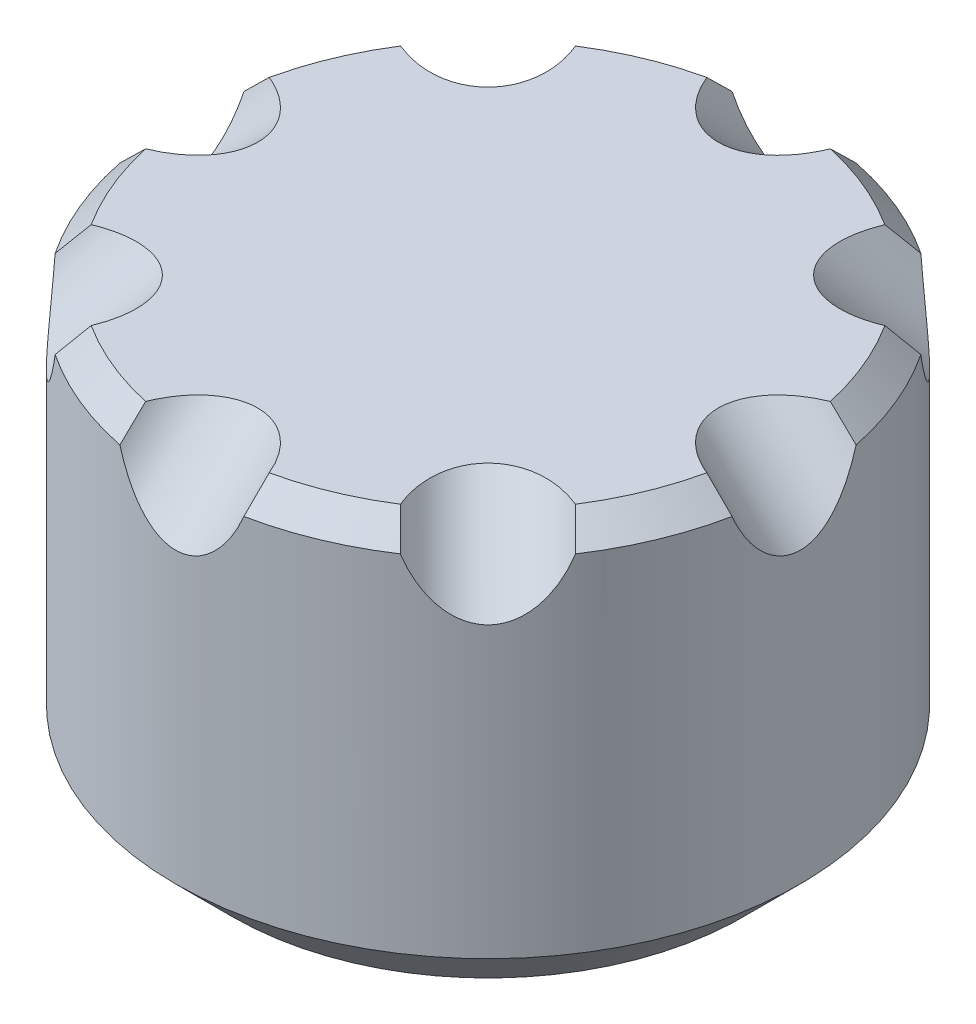
SolidWorks part; units mm, degrees
ref_plane "Front Plane" through (0, 0, 0) normal (0, 0, 1) x (1, 0, 0)
ref_plane "Top Plane" through (0, 0, 0) normal (0, 1, 0) x (1, 0, 0)
ref_plane "Right Plane" through (0, 0, 0) normal (1, 0, 0) x (0, 0, -1)
sketch "Sketch1" plane through (0, 0, 0) normal (0, 1, 0) x (1, 0, 0)
  circle A0 centre (0, 0) radius 8.75
  dimension "D1" = 17.5
extrude "Boss-Extrude1" add sketch "Sketch1" along normal blind 12
sketch "Sketch2" plane through (0, 0, 0) normal (0, -1, 0) x (1, 0, 0)
  line L0 (-2.5981, 1.5) -> (2.5981, 1.5) construction
  line L1 (-2.6439, 1.58) -> (2.6439, 1.58)
  arc A0 (-2.5981, 1.5) -> (2.5981, 1.5) centre (0, 0) ccw construction
  arc A1 (-2.6439, 1.58) -> (2.6439, 1.58) centre (0, 0) ccw
  point P5 (0, -3)
  dimension "D1" = 6
  dimension "D2" = 4.5
  dimension "D3" = 0.08
extrude "Cut-Extrude1" cut sketch "Sketch2" against normal offset from surface (11.4 mm away) 0.6 up to face at (0, 12, 8.75)
sketch "Sketch3" plane through (0, 0, 0) normal (0, -1, 0) x (1, 0, 0)
  circle A0 centre (0, 0) radius 3.08
  arc A1 (-2.6439, 1.58) -> (2.6439, 1.58) centre (0, 0) ccw construction
sketch "Sketch4" plane through (0, 0, 0) normal (0, -1, 0) x (1, 0, 0)
  circle A0 centre (0, 0) radius 4.08
  arc A1 (-2.6439, 1.58) -> (2.6439, 1.58) centre (0, 0) ccw construction
  dimension "D1" = 1
extrude "Cut-Extrude2" cut sketch "Sketch3" against normal offset from surface (6.9 mm away) 4.5 contours A0 up to face at (0, 11.4, -0.75)
extrude "Cut-Extrude3" cut sketch "Sketch4" against normal offset from surface (4.4 mm away) 7 up to face at (0, 11.4, -0.75)
chamfer "Chamfer1" distance 0.5 angle 30 1 edges at (0, 4.4, 3.08) first distance on face at (0, 4.4, 3.08)
chamfer "Chamfer2" distance 1.6 angle 45 1 edges at (0, 0, 8.75)
chamfer "Chamfer3" distance 0.7 angle 45 1 edges at (0, 12, 8.75)
sketch "Sketch5" plane through (0, 0, 0) normal (1, 0, 0) x (0, 0, -1)
  line L0 (7.5375, 13.7409) -> (17.4543, 3.8241) construction
  line L1 (7.5375, 13.7409) -> (7.5375, 19.1886) construction
  line L2 (5.8642, 15.4142) -> (4.45, 14)
  line L3 (4.45, 14) -> (11.5211, 6.9289)
  line L4 (11.5211, 6.9289) -> (12.9353, 8.3431)
  line L5 (5.8642, 15.4142) -> (12.9353, 8.3431)
  line L6 (8.05, 12) -> (-8.05, 12) construction
  line L8 (8.75, 1.6) -> (8.75, 11.3) construction
  dimension "D1" = 45
  dimension "D2" = 2
  dimension "D3" = 2
  dimension "D4" = 10
  dimension "D5" = 4.3
revolve "Cut-Revolve1" cut sketch "Sketch5" angle 360 about L0
pattern_circular "CirPattern1" count 8 over 360 about axis through (0, 12, 0) along (0, -1, 0) of "Cut-Revolve1" reverse direction yes
